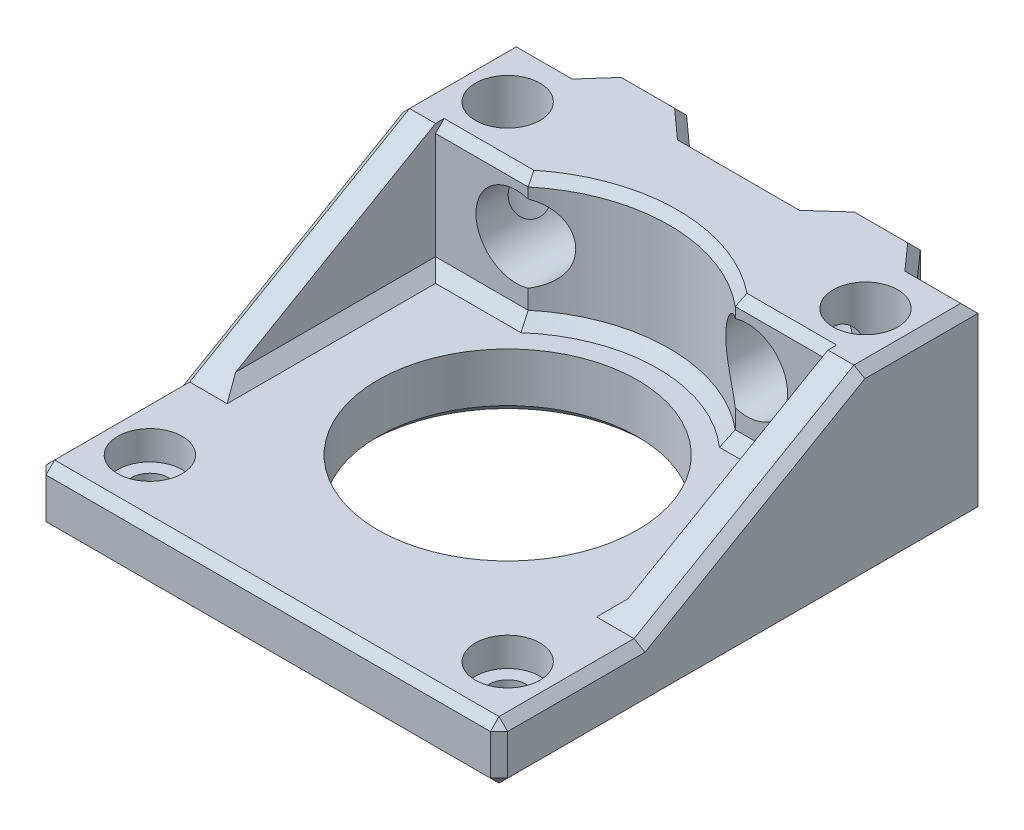
SolidWorks part; units mm, degrees
ref_plane "Front Plane" through (0, 0, 0) normal (0, 0, 1) x (1, 0, 0)
ref_plane "Top Plane" through (0, 0, 0) normal (0, 1, 0) x (1, 0, 0)
ref_plane "Right Plane" through (0, 0, 0) normal (1, 0, 0) x (0, 0, -1)
sketch "Sketch1" plane through (0, 0, 0) normal (0, 1, 0) x (1, 0, 0)
  line L0 (0, 0) -> (0, 11.25) construction
  line L1 (-20, 20.75) -> (-14.75, 20.75)
  line L2 (-20, 20.75) -> (-20, -20.75)
  line L3 (-20, -20.75) -> (20, -20.75)
  line L4 (20, 20.75) -> (20, -20.75)
  line L5 (0, 11.25) -> (0, 20.75) construction
  line L6 (-14.75, 20.75) -> (-12.75, 23)
  line L7 (-5, 20.75) -> (5, 20.75)
  line L8 (5, 20.75) -> (7.5, 23)
  line L9 (14.75, 20.75) -> (20, 20.75)
  line L10 (-12.75, 23) -> (-7.5, 23)
  line L11 (-7.5, 23) -> (-5, 20.75)
  line L12 (7.5, 23) -> (12.75, 23)
  line L13 (12.75, 23) -> (14.75, 20.75)
  line L14 (0, -20.75) -> (0, -11.25) construction
  line L15 (-15.5, -15.5) -> (15.5, -15.5) construction
  line L16 (-15.5, -15.5) -> (-15.5, 15.5) construction
  line L17 (-15.5, 15.5) -> (15.5, 15.5) construction
  line L18 (15.5, -15.5) -> (15.5, 15.5) construction
  line L19 (-15.5, -15.5) -> (15.5, 15.5) construction
  line L20 (-15.5, 15.5) -> (15.5, -15.5) construction
  circle A0 centre (0, 0) radius 11.25
  circle A1 centre (15.5, 15.5) radius 1.6
  circle A2 centre (-15.5, 15.5) radius 1.6
  circle A3 centre (-15.5, -15.5) radius 1.6
  circle A4 centre (15.5, -15.5) radius 1.6
  point P19 (0, 20.75)
  dimension "D1" = 22.5
  dimension "D10" = 3.2
  dimension "D2" = 9.5
  dimension "D3" = 40
  dimension "D4" = 25.5
  dimension "D5" = 29.5
  dimension "D6" = 10
  dimension "D7" = 2.25
  dimension "D8" = 15
  dimension "D9" = 31
extrude "Boss-Extrude1" add sketch "Sketch1" along normal blind 5
sketch "Sketch4" plane through (0, 5, 0) normal (0, 1, 0) x (1, 0, 0)
  circle A0 centre (-15.5, -15.5) radius 2.8
  circle A1 centre (15.5, 15.5) radius 2.8
  circle A2 centre (-15.5, 15.5) radius 2.8
  circle A3 centre (15.5, -15.5) radius 2.8
  circle A4 centre (15.5, -15.5) radius 1.6 construction
  circle A5 centre (-15.5, -15.5) radius 1.6 construction
  circle A6 centre (-15.5, 15.5) radius 1.6 construction
  circle A7 centre (15.5, 15.5) radius 1.6 construction
  dimension "D1" = 5.6
extrude "Cut-Extrude1" cut sketch "Sketch4" against normal offset from surface (2.5 mm away) 2.5 up to face at (0, 0, -14.5833)
sketch "Sketch2" plane through (0, 5, 0) normal (0, 1, 0) x (1, 0, 0)
  line L0 (0, 14) -> (0, 0) construction
  line L1 (-8.9687, 10.75) -> (-20, 10.75)
  line L2 (-20, 20.75) -> (-20, -20.75) construction
  line L3 (-20, 10.75) -> (-20, 20.75)
  line L5 (20, 20.75) -> (20, 10.75)
  line L6 (20, -20.75) -> (20, 20.75) construction
  line L7 (20, 10.75) -> (8.9687, 10.75)
  line L12 (-20, 20.75) -> (-14.75, 20.75)
  line L13 (-14.75, 20.75) -> (-12.75, 23)
  line L14 (-12.75, 23) -> (-7.5, 23)
  line L15 (-7.5, 23) -> (-5, 20.75)
  line L16 (-5, 20.75) -> (5, 20.75)
  line L17 (5, 20.75) -> (7.5, 23)
  line L18 (7.5, 23) -> (12.75, 23)
  line L19 (12.75, 23) -> (14.75, 20.75)
  line L20 (14.75, 20.75) -> (20, 20.75)
  arc A0 (-8.9687, 10.75) -> (8.9687, 10.75) centre (0, 0) cw
  circle A1 centre (-15.5, 15.5) radius 2.8
  circle A2 centre (15.5, 15.5) radius 2.8
  circle A5 centre (-15.5, 15.5) radius 2.8 construction
  circle A6 centre (15.5, 15.5) radius 2.8 construction
  line M3 (-20, 20.75) -> (-20, -20.75)
  line M5 (20, -20.75) -> (20, 20.75)
  line M6 (-14.75, 20.75) -> (-20, 20.75)
  line M8 (20, 20.75) -> (14.75, 20.75)
  line M9 (14.75, 20.75) -> (12.75, 23)
  line M10 (12.75, 23) -> (7.5, 23)
  line M11 (7.5, 23) -> (5, 20.75)
  line M12 (5, 20.75) -> (-5, 20.75)
  line M13 (-5, 20.75) -> (-7.5, 23)
  line M14 (-7.5, 23) -> (-12.75, 23)
  line M15 (-12.75, 23) -> (-14.75, 20.75)
  circle M44 centre (-15.5, 15.5) radius 2.8
  circle M45 centre (15.5, 15.5) radius 2.8
  dimension "D1" = 14
  dimension "D2" = 10
extrude "Boss-Extrude2" add sketch "Sketch2" along normal offset from surface (11 mm away) 16 contours L1 A0 L7 M5 M8 M9 M10 M11 M12 M13 M14 M15 M6 M3 M45 M44 region at (0, 5, -16.801) up to face at (0, 0, -14.5833)
sketch "Sketch3" plane through (20, 0, 0) normal (1, 0, 0) x (0, 0, -1)
  line L0 (10.75, 16) -> (-8.3026, 5)
  line L1 (-20.75, 5) -> (10.75, 5) construction
  line L2 (-8.3026, 5) -> (10.75, 5)
  line L4 (10.75, 5) -> (10.75, 16)
  point P9 (10.75, 5)
  point P11 (10.6458, 5)
  dimension "D1" = 60
extrude "Boss-Extrude3" add sketch "Sketch3" against normal blind 3
mirror "Mirror1" about plane through (0, 0, 0) normal (1, 0, 0) of "Boss-Extrude3"
chamfer "Chamfer2" distance 1 angle 45 5 edges at (17, 5, -1.2237) (12.9843, 5, -10.75) (0, 5, -14) (-12.9843, 5, -10.75) (-17, 5, -1.2237)
sketch "Sketch5" plane through (0, 0, -10.75) normal (0, 0, 1) x (1, 0, 0)
  line L0 (-10, 16) -> (-10, 11) construction
  line L1 (-8.9687, 16) -> (-17, 16) construction
  line L2 (10, 11) -> (17, 11) construction
  line L3 (17, 6) -> (17, 16) construction
  line L4 (10, 11) -> (-10, 11) construction
  line L5 (-10, 11) -> (-17, 11) construction
  line L7 (-17, 6) -> (-17, 16) construction
  line L8 (-10, 11) -> (-10, 5) construction
  line L9 (-8.5987, 5) -> (-16, 5) construction
  circle A0 centre (-10, 11) radius 2.1
  circle A1 centre (10, 11) radius 2.1
  dimension "D2" = 4.2
  dimension "D1" = 20
  dimension "D3" = 5
extrude "Cut-Extrude2" cut sketch "Sketch5" against normal up to next
sketch "Sketch6" plane through (0, 0, -10.75) normal (0, 0, 1) x (1, 0, 0)
  circle A0 centre (-10, 11) radius 3.5
  circle A1 centre (10, 11) radius 3.5
  arc A2 (-8.9687, 12.8293) -> (-8.9687, 9.1707) centre (-10, 11) ccw construction
  arc A3 (8.9687, 9.1707) -> (8.9687, 12.8293) centre (10, 11) ccw construction
  dimension "D1" = 7
extrude "Cut-Extrude3" cut sketch "Sketch6" against normal offset from surface (7 mm away) 3 up to face at (17.375, 8, -20.75)
chamfer "Chamfer3" distance 0.75 angle 45 38 edges at (15.5, 0, 17.1) (-15.5, 0, 17.1) (-15.5, 0, -13.9) (15.5, 0, -13.9) (0, 0, 11.25) (12.9843, 16, -10.75) (0, 16, -14) (-12.9843, 16, -10.75) (0, 0, 20.75) (20, 0, 0) (17.375, 0, -20.75) (13.75, 0, -21.875) (10.125, 0, -23) (6.25, 0, -21.875) (0, 0, -20.75) (-6.25, 0, -21.875) (-10.125, 0, -23) (-13.75, 0, -21.875) (-17.375, 0, -20.75) (-20, 0, 0) (20, 2.5, 20.75) (-20, 2.5, 20.75) (-20, 5, 14.5263) (-20, 10.5, -1.2237) (-20, 16, -15.75) (-17.375, 16, -20.75) (-13.75, 16, -21.875) (-10.125, 16, -23) (-6.25, 16, -21.875) (0, 16, -20.75) (6.25, 16, -21.875) (10.125, 16, -23) (13.75, 16, -21.875) (17.375, 16, -20.75) (20, 16, -15.75) (20, 10.5, -1.2237) (20, 5, 14.5263) (0, 5, 20.75)
equation "\"Tolerance\"=0.2"
equation "\"D10@Sketch1\"=3 + \"Tolerance\""
equation "\"D1@Sketch4\"=5.4 + \"Tolerance\""
equation "\"D2@Sketch5\"=4 + \"Tolerance\""
equation "\"D1@Sketch6\"=6.8 + \"Tolerance\""
